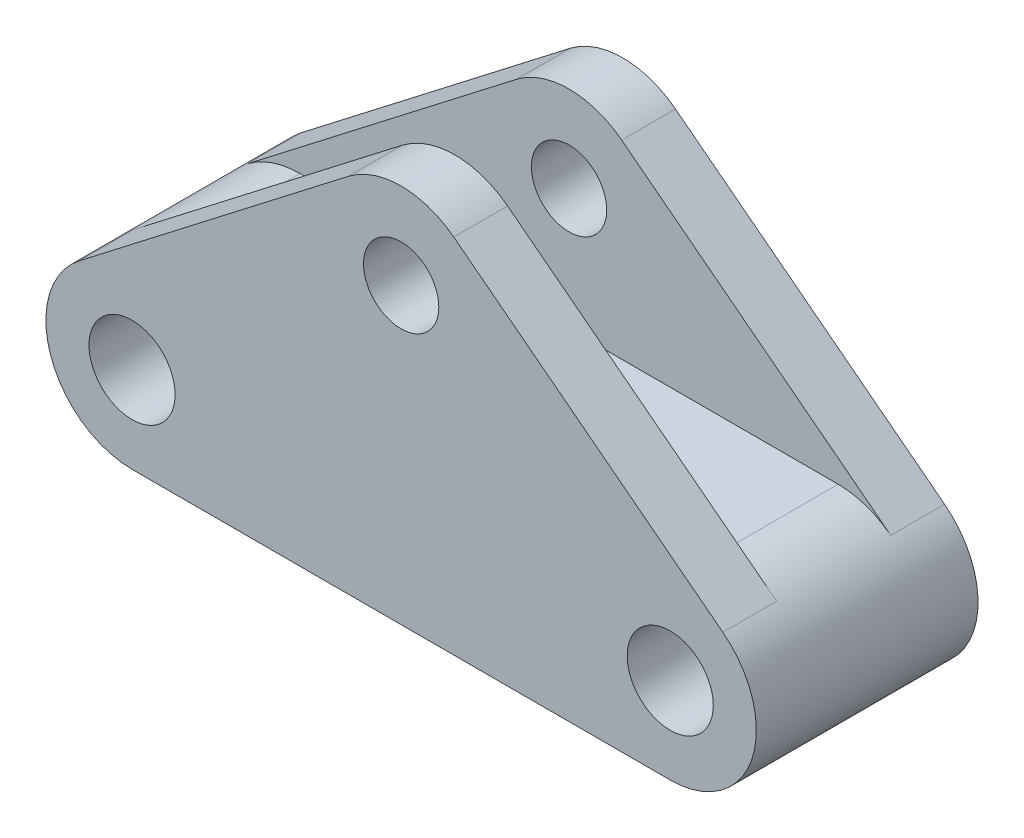
SolidWorks part; units mm, degrees
material "ABS"
ref_plane "Front Plane" through (0, 0, 0) normal (0, 0, 1) x (1, 0, 0)
ref_plane "Top Plane" through (0, 0, 0) normal (0, 1, 0) x (1, 0, 0)
ref_plane "Right Plane" through (0, 0, 0) normal (1, 0, 0) x (0, 0, -1)
sketch "Sketch1" plane through (0, 0, 0) normal (0, 0, 1) x (1, 0, 0)
  line L0 (0, 27.2364) -> (0, -32.7408) construction
  line L1 (25, -27.3) -> (-25, -27.3)
  line L2 (-29.8887, -12.9675) -> (-4.8887, 6.3325)
  line L3 (29.8887, -12.9675) -> (4.8887, 6.3325)
  line L4 (-25, -11.3) -> (25, -11.3)
  circle A0 centre (0, 0) radius 3.5
  circle A1 centre (0, 0) radius 11
  circle A2 centre (-25, -19.3) radius 4
  arc A3 (-25, -27.3) -> (-29.8887, -12.9675) centre (-25, -19.3) cw
  arc A4 (-4.8887, 6.3325) -> (4.8887, 6.3325) centre (0, 0) cw
  arc A5 (25, -27.3) -> (29.8887, -12.9675) centre (25, -19.3) ccw
  circle A6 centre (25, -19.3) radius 4
  arc A7 (-25, -11.3) -> (-29.8887, -12.9675) centre (-25, -19.3) ccw
  arc A8 (25, -11.3) -> (29.8887, -12.9675) centre (25, -19.3) cw
  point P8 (0, 11)
  point P15 (0, -27.3)
  point P21 (0, -11.3)
  dimension "D1" = 7
  dimension "D2" = 22
  dimension "D3" = 8
  dimension "D6" = 8
  dimension "D7" = 8
  dimension "D4" = 25
  dimension "D5" = 30.3
extrude "Boss-Extrude1" add sketch "Sketch1" against normal blind 5 contours L0 L4 A7 A3 L1 A2 | L4 L0 L1 A5 A8 A6 | A1 L0 L4 A8 L3 | A4 L0 A0 A1 L3 | L0 A4 L2 A1 A0 | L0 A1 L2 A7 L4 region at (4.9704, -1.8523, 0) region at (-4.9704, -1.8523, 0) region at (14.8622, -7.4078, 0) region at (-14.8622, -7.4078, 0) region at (14.6535, -19.3, 0) region at (-14.6535, -19.3, 0)
extrude "Boss-Extrude2" add sketch "Sketch1<3>" against normal blind 10.6 from vertex contours L0 L4 A7 A3 L1 A2 | L4 L0 L1 A5 A8 A6 region at (14.6535, -19.3, 0) region at (-14.6535, -19.3, 0) starting at point (-29.8887, -12.9675, -5)
sketch "Sketch1<3>" plane through (0, 0, 0) normal (0, 0, 1) x (1, 0, 0) same geometry as "Sketch1"
extrude "Boss-Extrude3" add sketch "Sketch1<4>" against normal blind 5 from vertex contours L0 A1 L2 A7 L4 | L0 A4 L2 A1 A0 | A4 L0 A0 A1 L3 | A1 L0 L4 A8 L3 | L4 L0 L1 A5 A8 A6 | L0 L4 A7 A3 L1 A2 region at (4.9704, -1.8523, 0) region at (-4.9704, -1.8523, 0) region at (14.8622, -7.4078, 0) region at (-14.8622, -7.4078, 0) region at (14.6535, -19.3, 0) region at (-14.6535, -19.3, 0) starting at point (-25, -27.3, -15.6)
sketch "Sketch1<4>" plane through (0, 0, 0) normal (0, 0, 1) x (1, 0, 0) same geometry as "Sketch1"
equation "\"rod_diameter\"= 8"
equation "\"rod_hole_thickness\"= 4"
equation "\"rod_radius\"= \"rod_diameter\" / 2"
equation "\"platter_diameter\"= 320"
equation "\"platter_radius\"= \"platter_diameter\" / 2"
equation "\"extruder_mount_hole_spacing\"= 75"
equation "\"arm_rod_spacing\"= 40"
equation "\"top_frame_rod_spacing\"= \"arm_rod_spacing\" + 40"
equation "\"motor_level_rod_spacing\"= 15"
equation "\"linear_bearing_diameter\"= 15"
equation "\"z_rod_spacing\"= 75"
equation "\"platter_rod_spacing\"= 50"
equation "\"rod_nut_thickness\"= 6.5"
equation "\"rod_nut_inscribed_diameter\"= 13"
equation "\"z_height\"= 350"
equation "\"D1@Sketch1\"=\"rod_diameter\"-1"
equation "\"D3@Sketch1\"=\"rod_diameter\""
equation "\"D4@Sketch1\"=\"platter_rod_spacing\"/2"
equation "\"D6@Sketch1\"=\"rod_radius\"+\"rod_hole_thickness\""
equation "\"D7@Sketch1\"=\"rod_radius\"+\"rod_hole_thickness\""
